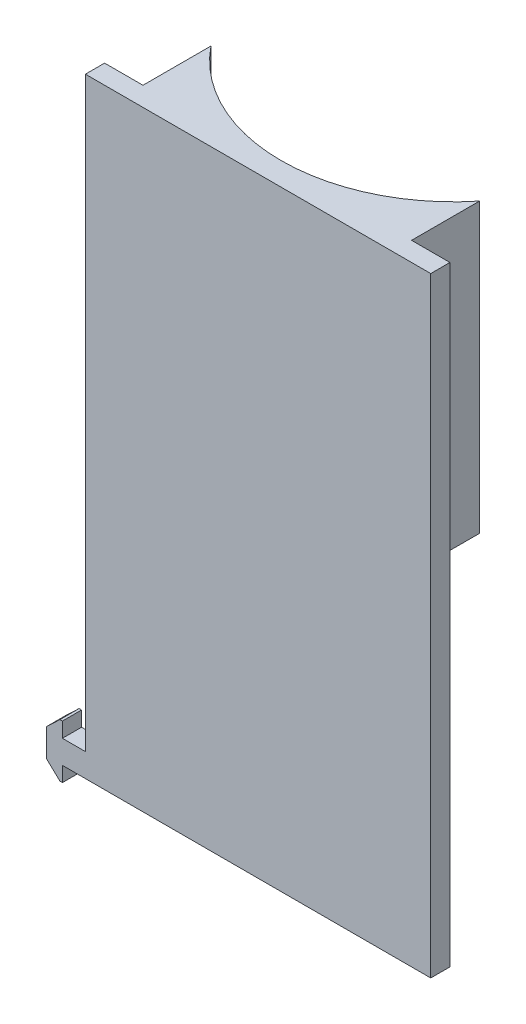
SolidWorks part; units mm, degrees
ref_plane "Front Plane" through (0, 0, 0) normal (0, 0, 1) x (1, 0, 0)
ref_plane "Top Plane" through (0, 0, 0) normal (0, 1, 0) x (1, 0, 0)
ref_plane "Right Plane" through (0, 0, 0) normal (1, 0, 0) x (0, 0, -1)
sketch "Sketch2" plane through (0, 0, 0) normal (0, 0, 1) x (1, 0, 0)
  line L1 (-5.1524, -3.6183) -> (-1.6411, -6.95)
  line L2 (-1.6411, -6.95) -> (-1, -6.95)
  line L6 (-5.1524, -3.6183) -> (-5.1524, 3.6183)
  line L7 (-1, -6.95) -> (-1, 6.95)
  line L8 (0, 0) -> (-6.1524, 0) construction
  line L9 (-1.6411, 6.95) -> (-1, 6.95)
  line L10 (-5.1524, 3.6183) -> (-1.6411, 6.95)
  line L11 (-1, -3.05) -> (5, -3.05)
  line L12 (-1, 3.05) -> (5, 3.05)
  line L13 (5, -3.05) -> (95, -3.05)
  line L14 (5, 3.05) -> (5, 155.95)
  line L15 (5, 155.95) -> (95, 155.95)
  line L16 (95, 155.95) -> (95, -3.05)
  line L17 (-1, 3.05) -> (-1, -3.05)
  point P11 (-1, 0)
  point P13 (-5.1524, 0)
  line B0 (0, -7.95) -> (-2.04, -7.95)
  line B1 (-6.1524, -4.048) -> (-6.1524, 4.048)
  line B2 (-2.04, 7.95) -> (0, 7.95)
  line B3 (0, 7.95) -> (0, -7.95)
  line B4 (-2.04, -7.95) -> (-6.1524, -4.048)
  line B5 (-6.1524, 4.048) -> (-2.04, 7.95)
  line B6 (0, -4.05) -> (0, 4.05) construction
  dimension "D1" = 1
  dimension "D2" = 1
  dimension "D3" = 1
  dimension "D4" = 1
  dimension "D5" = 1
  dimension "D6" = 6
  dimension "D7" = 90
  dimension "D8" = 159
sketch_block_instance "Extrusion Profile-2"
sketch_block "Block1" parameters "D1"=8.44, "D2"=2.6, "D3"=6, "D4"=16.7, "D6"=5.6686, "D7"=2.0404, "D8"=8.0963, "D9"=15.9, "D5"=2.4157
extrude "Boss-Extrude1" add sketch "Sketch2" against normal blind 5 contours L8 L17 L7 L9 L10 L6 | L7 L8 L6 L1 L2 | L12 B3 L11 L13 L16 L15 L14 | B3 L8 L7 L11 | L8 B3 L12 L17 region at (-2.846, -2.8739, 0) region at (-2.846, 2.8739, 0) region at (-0.5, -1.525, 0) region at (-0.5, 1.525, 0) region at (49.899, 76.2874, 0)
sketch "Sketch3" plane through (0, 155.95, 0) normal (0, 1, 0) x (1, 0, 0)
  line L0 (5, 5) -> (5, 0) construction
  line L1 (95, 5) -> (95, 0) construction
  line L2 (5, 51) -> (95, 51) construction
  line L3 (15, 22.7157) -> (15, 5)
  line L4 (5, 5) -> (95, 5) construction
  line L5 (15, 5) -> (85, 5)
  line L6 (50, 0) -> (50, -5.3878) construction
  line L7 (5, 0) -> (95, 0) construction
  line L8 (85, 22.7157) -> (85, 5)
  arc A0 (5, 51) -> (95, 51) centre (50, 51) ccw
  arc A1 (15, 22.7157) -> (85, 22.7157) centre (50, 51) ccw
  line M7 (95, 5) -> (5, 5)
  dimension "D1" = 45
  dimension "D2" = 46
  dimension "D3" = 35
extrude "Boss-Extrude2" add sketch "Sketch3" against normal blind 75 contours A0 L3 L8 M7 region at (50, 155.95, -5.2779)
